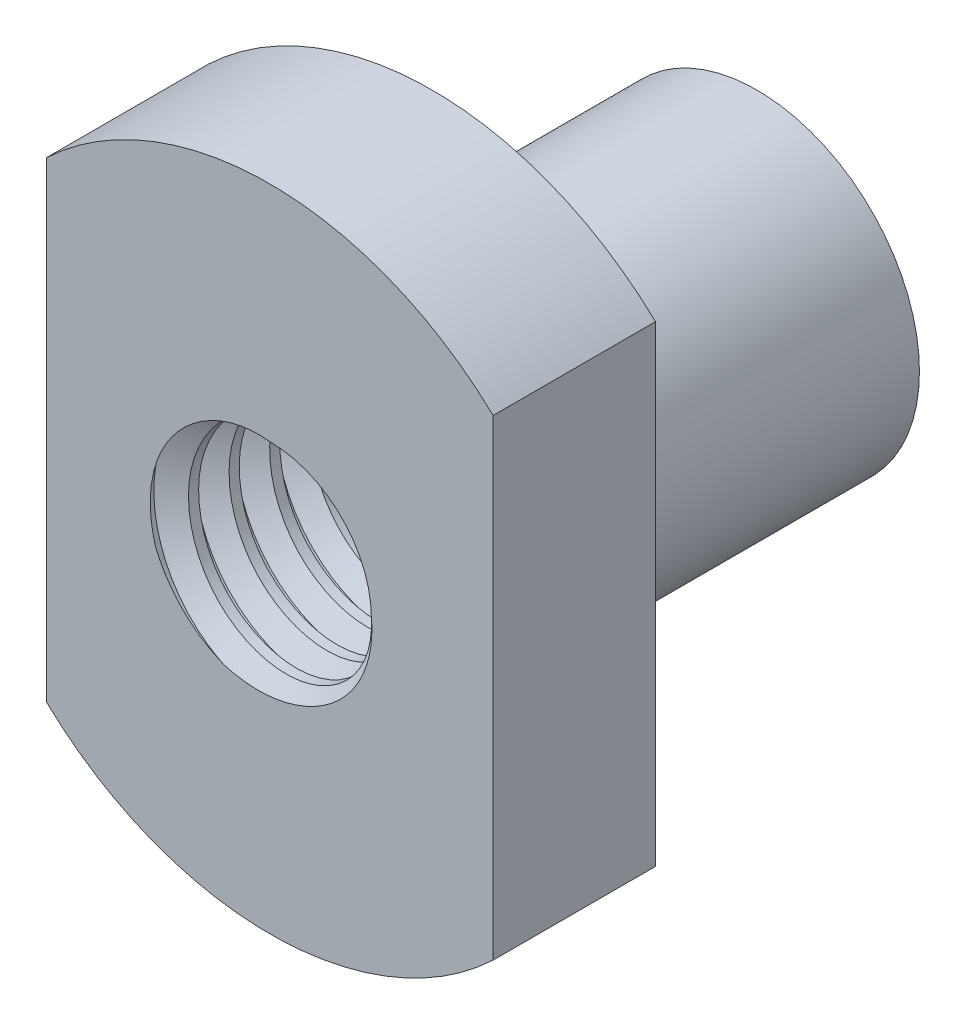
SolidWorks part; units mm, degrees
ref_plane "Piano frontale" through (0, 0, 0) normal (0, 0, 1) x (1, 0, 0)
ref_plane "Piano superiore" through (0, 0, 0) normal (0, 1, 0) x (1, 0, 0)
ref_plane "Piano destro" through (0, 0, 0) normal (1, 0, 0) x (0, 0, -1)
sketch "Schizzo1" plane through (0, 0, 0) normal (0, 0, 1) x (1, 0, 0)
  circle A0 centre (0, 0) radius 2
extrude "Estrusione-Estrusione1" add sketch "Schizzo1" along normal blind 4
sketch "Schizzo2" plane through (0, 0, 4) normal (0, 0, 1) x (1, 0, 0)
  circle A0 centre (0, 0) radius 4
extrude "Estrusione-Estrusione2" add sketch "Schizzo2" along normal blind 2
sketch "Schizzo3" plane through (0, 0, 6) normal (0, 0, 1) x (1, 0, 0)
  line L0 (-2.75, 0) -> (2.75, 0) construction
  line L1 (-2.75, 2.9047) -> (-2.75, -2.9047)
  line L2 (2.75, 2.9047) -> (2.75, -2.9047)
  circle A0 centre (0, 0) radius 4 construction
  arc A1 (2.75, -2.9047) -> (2.75, 2.9047) centre (0, 0) ccw
  arc A2 (-2.75, -2.9047) -> (-2.75, 2.9047) centre (0, 0) cw
  point P4 (0, 0)
  point P10 (-2.75, 0)
  point P13 (2.75, 0)
extrude "Taglio-Estrusione1" cut sketch "Schizzo3" against normal blind 2
hole_wizard "Preforo da maschiare M3x0.5-1" positions "Schizzo4" profile "Schizzo5" hole size "M3x0.5" standard "Ansi Metric"
sketch "Schizzo4" plane through (0, 0, 0) normal (0, 0, -1) x (-1, 0, 0)
  point P0 (0, 0)
sketch "Schizzo5" plane through (0, 0, 0) normal (1, 0, 0) x (0, 1, 0)
  line L0 (0, 0) -> (0, 40)
  line L1 (0, 40) -> (1.25, 39.2489)
  line L2 (1.25, 39.2489) -> (1.25, 0)
  line L5 (1.25, 0) -> (0, 0)
  line L10 (0, 40) -> (-1.25, 39.2489) construction
  line L11 (0, -6.35) -> (0, 107.95) construction
  dimension "Hole Dia." = 2.5
  dimension "Hole Depth" = 40
  dimension "Drill Angle" = 118
thread "Filettatura1" pitch 0.5 method cut profile "Profilo filettatura1" start angle 0, offset 0, length 10, pitch 0.5, diameter 2.5
ref_plane "Piano1" through (1.25, 0, 0) normal (0, -1, 0) x (1, 0, 0)
sketch "Profilo filettatura1" plane through (1.25, 0, 0) normal (0, -1, 0) x (1, 0, 0)
  line L0 (0, 0) -> (0, 0.5) construction
  line L1 (0, 0) -> (0.2706, 0.1562)
  line L2 (0.2706, 0.1562) -> (0.2706, 0.2187)
  line L3 (0.2706, 0.2187) -> (0, 0.375)
  line L4 (0.2706, 0.1875) -> (0, 0.1875) construction
  line L11 (0, 0) -> (0, 0.375)
  point P2 (0, 0)
  dimension "Pitch" = 0.5
  dimension "Profile_Angle" = 60
  dimension "Profile_Land" = 0.0625
  dimension "Profile_Height" = 0.2706
